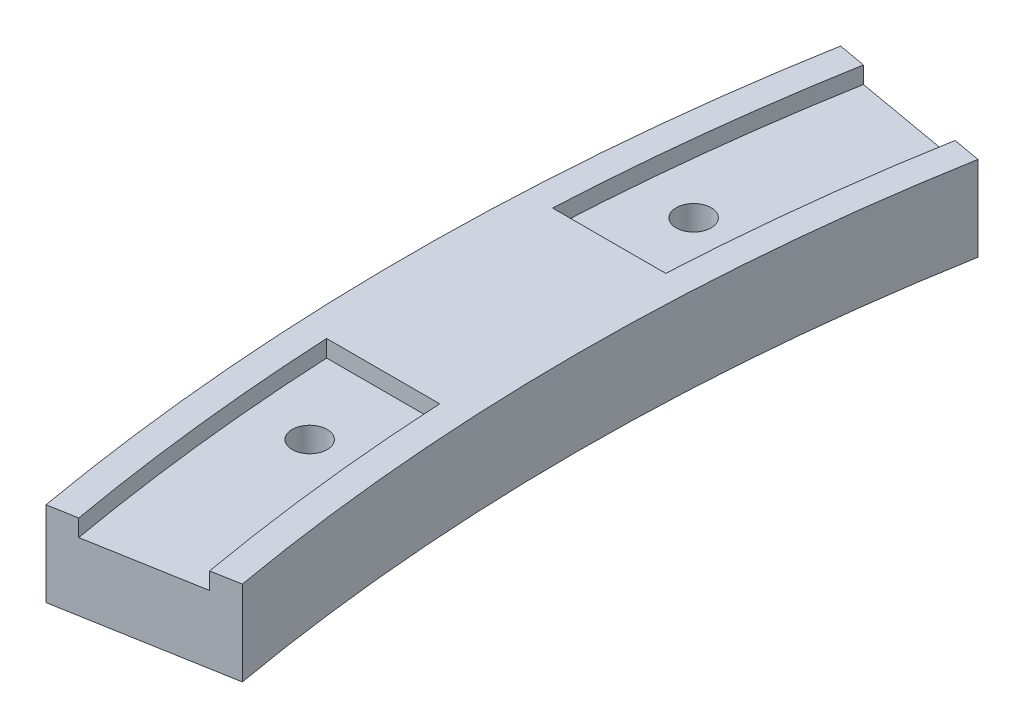
SolidWorks part; units mm, degrees
ref_plane "Front Plane" through (0, 0, 0) normal (0, 0, 1) x (1, 0, 0)
ref_plane "Top Plane" through (0, 0, 0) normal (0, 1, 0) x (1, 0, 0)
ref_plane "Right Plane" through (0, 0, 0) normal (1, 0, 0) x (0, 0, -1)
sketch "Sketch1" plane through (0, 0, 0) normal (0, 1, 0) x (1, 0, 0)
  line L0 (0, 0) -> (-199.4236, -35.1638) construction
  line L1 (0, 0) -> (-199.4236, 35.1638) construction
  line L2 (0, 0) -> (-195, 0) construction
  line L3 (-199.4236, 35.1638) -> (-184.6515, 32.559)
  line L4 (-184.6515, -32.559) -> (-199.4236, -35.1638)
  arc A0 (-196.9616, 34.7296) -> (-196.9616, -34.7296) centre (0, 0) ccw construction
  arc A1 (-187.1135, 32.9932) -> (-187.1135, -32.9932) centre (0, 0) ccw construction
  arc A2 (-192.0375, -33.8614) -> (-192.0375, 33.8614) centre (0, 0) cw construction
  arc A3 (-199.4236, 35.1638) -> (-199.4236, -35.1638) centre (0, 0) ccw
  arc A4 (-184.6515, 32.559) -> (-184.6515, -32.559) centre (0, 0) ccw
  dimension "D1" = 200
  dimension "D2" = 190
  dimension "D3" = 5
  dimension "D5" = 2.5
  dimension "D6" = 2.5
  dimension "D4" = 20
extrude "Boss-Extrude1" add sketch "Sketch1" along normal blind 7.5
sketch "Sketch2" plane through (0, 7.5, 0) normal (0, 1, 0) x (1, 0, 0)
  line L2 (0, 0) -> (-195, 0) construction
  line L3 (0, 0) -> (-199.4236, -35.1638) construction
  line L4 (0, 0) -> (-199.4236, 35.1638) construction
  line L5 (0, 0) -> (-190, 0) construction
  line L6 (0, 0) -> (-199.4236, -35.1638) construction
  line L7 (0, 0) -> (-199.4236, 35.1638) construction
  line L8 (0, 10) -> (-202.2529, 10) construction
  line L9 (0, 10) -> (0, -10) construction
  line L10 (0, -10) -> (-202.2529, -10) construction
  line L11 (-196.9616, 34.7296) -> (-187.1135, 32.9932)
  line L12 (-196.9616, -34.7296) -> (-187.1135, -32.9932)
  line L13 (-199.7498, -10) -> (-189.7367, -10)
  line L14 (-189.7367, 10) -> (-199.7498, 10)
  arc A0 (-196.9616, 34.7296) -> (-196.9616, -34.7296) centre (0, 0) ccw construction
  arc A1 (-187.1135, 32.9932) -> (-187.1135, -32.9932) centre (0, 0) ccw construction
  arc A2 (-196.9616, 34.7296) -> (-196.9616, -34.7296) centre (0, 0) ccw
  arc A3 (-187.1135, 32.9932) -> (-187.1135, -32.9932) centre (0, 0) ccw
  arc A4 (-199.4236, 35.1638) -> (-199.4236, -35.1638) centre (0, 0) ccw construction
  line M2 (-199.4236, -35.1638) -> (-184.6515, -32.559)
  line M4 (-184.6515, 32.559) -> (-199.4236, 35.1638)
  dimension "D1" = 20
extrude "Cut-Extrude1" cut sketch "Sketch2" against normal blind 1.5 contours A3 A2 L14 M4 | A3 L13 A2 M2 region at (-193.6958, 7.5, -21.9638) region at (-193.6958, 7.5, 21.9638)
ref_plane "Plane1" through (-195, 0, 0) normal (1, 0, 0) x (0, 0, -1)
sketch "Sketch6" plane through (0, 0, 0) normal (0, -1, 0) x (1, 0, 0)
  line L0 (0, 0) -> (-194.258, 16.9954) construction
  line L1 (0, 0) -> (-195, 0) construction
  line L2 (0, 0) -> (-195, 0) construction
  line L3 (0, 0) -> (-194.258, -16.9954) construction
  arc A0 (-192.0375, 33.8614) -> (-192.0375, -33.8614) centre (0, 0) ccw construction
  dimension "D1" = 5
hole_wizard "Ø3.1 (3.1) Diameter Hole1" positions "Sketch7" profile "Sketch8" hole size "Ø3.1" standard "ISO" end condition through all
sketch "Sketch7" plane through (0, 0, 0) normal (0, -1, 0) x (-1, 0, 0)
  point P0 (194.258, -16.9954)
  point P3 (194.258, 16.9954)
sketch "Sketch8" plane through (-194.258, 0, 16.9954) normal (1, 0, 0) x (0, 0, -1)
  line L0 (0, 0) -> (0, 7.5)
  line L1 (0, 7.5) -> (1.55, 7.5)
  line L2 (1.55, 7.5) -> (1.55, 0)
  line L5 (1.55, 0) -> (0, 0)
  line L11 (0, -6.35) -> (0, 107.95) construction
  dimension "Thru Hole Dia." = 3.1
  dimension "Thru Hole Depth" = 7.5
